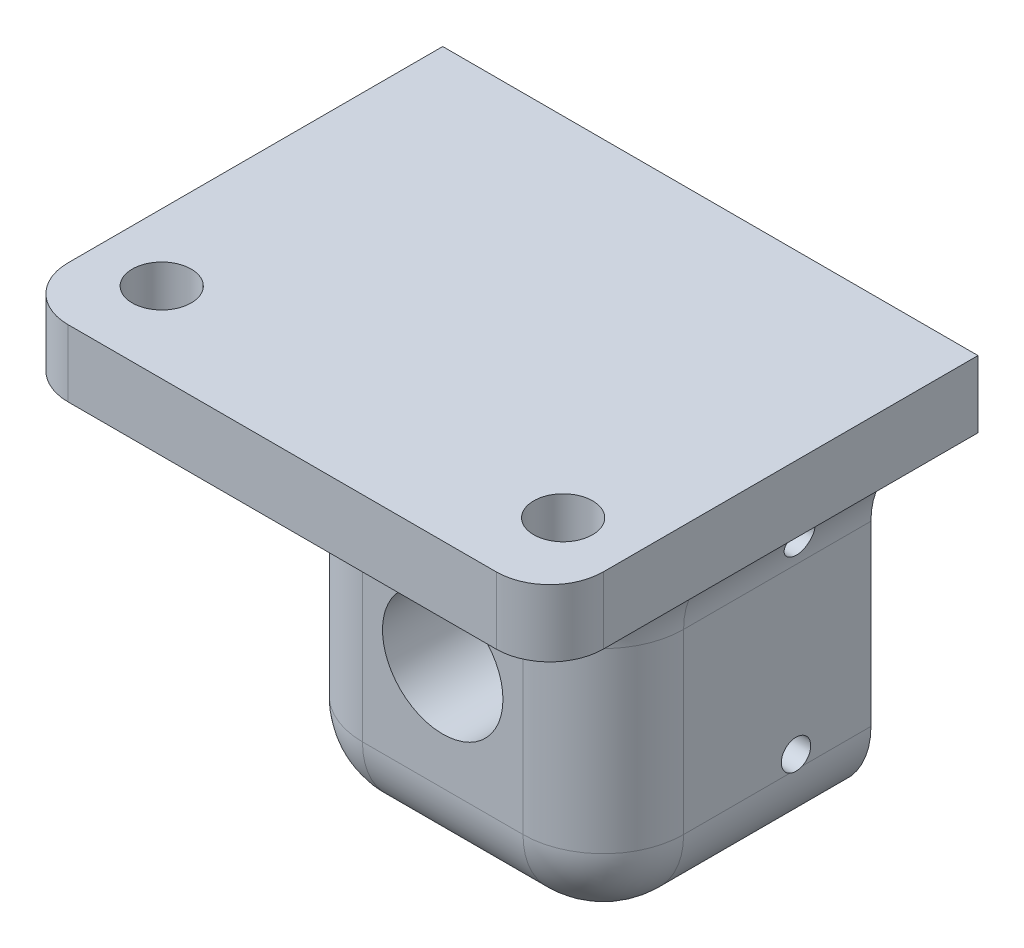
SolidWorks part; units mm, degrees
ref_plane "Plan de face" through (0, 0, 0) normal (0, 0, 1) x (1, 0, 0)
ref_plane "Plan de dessus" through (0, 0, 0) normal (0, 1, 0) x (1, 0, 0)
ref_plane "Plan de droite" through (0, 0, 0) normal (1, 0, 0) x (0, 0, -1)
sketch "Esquisse1" plane through (0, 0, 0) normal (0, 0, 1) x (1, 0, 0)
  line L1 (-20, 17) -> (20, 17)
  line L2 (-20, 17) -> (-20, -17)
  line L3 (-20, -17) -> (20, -17)
  line L4 (20, 17) -> (20, -17)
  dimension "D1" = 40
  dimension "D2" = 34
  dimension "D3" = 17
  dimension "D4" = 20
extrude "Boss.-Extru.1" add sketch "Esquisse1" along normal blind 20
sketch "Esquisse2" plane through (0, 0, 20) normal (0, 0, 1) x (1, 0, 0)
  line L1 (20, 17) -> (-20, 17)
  line L2 (20, 17) -> (20, 12)
  line L3 (20, 12) -> (-20, 12)
  line L4 (-20, 17) -> (-20, 12)
  line L5 (-20, 17) -> (-20, -17) construction
  dimension "D1" = 5
extrude "Boss.-Extru.3" add sketch "Esquisse2" along normal blind 20
sketch "Esquisse4" plane through (0, 0, 20) normal (0, 0, 1) x (1, 0, 0)
  line L0 (20, -17) -> (20, 12) construction
  line L1 (-20, -17) -> (20, -17) construction
  circle A0 centre (0, -3) radius 4.5
  dimension "D1" = 9
  dimension "D2" = 20
  dimension "D3" = 14
extrude "Enlèv. mat.-Extru.1" cut sketch "Esquisse4" against normal through all
sketch "Esquisse5" plane through (0, 0, 0) normal (0, 0, -1) x (-1, 0, 0)
  circle A0 centre (0, -3) radius 8.1
  dimension "D1" = 16.2
extrude "Enlèv. mat.-Extru.2" cut sketch "Esquisse5" against normal blind 12
sketch "Esquisse6" plane through (0, 0, 20) normal (0, 0, 1) x (1, 0, 0)
  line L0 (-20, 12) -> (-12, 5)
  line L1 (-12, 5) -> (-12, -17)
  line L2 (-20, -17) -> (20, -17) construction
  line L3 (-12, -17) -> (-20, -17)
  line L4 (-20, -17) -> (-20, 12)
  line L5 (20, 12) -> (12, 5)
  line L6 (12, 5) -> (12, -17)
  line L7 (12, -17) -> (20, -17)
  line L8 (20, -17) -> (20, 12)
  dimension "D1" = 8
  dimension "D2" = 8
  dimension "D3" = 22
  dimension "D4" = 22
extrude "Enlèv. mat.-Extru.3" cut sketch "Esquisse6" against normal through all
fillet "Congé3" radius 6 2 edges at (12, -17, 10) (-12, -17, 10)
fillet "Congé4" radius 6 2 edges at (12, 5, 10) (-12, 5, 10)
sketch "Esquisse7" plane through (-12, 0, 0) normal (-1, 0, 0) x (0, 0, 1)
  line L1 (12, 5.1) -> (12, -11.1) construction
  line L3 (20, -17) -> (0, -17) construction
  circle A0 centre (5.6, 4) radius 1.1
  circle A1 centre (5.6, -10) radius 1.1
  dimension "D1" = 2.2
  dimension "D2" = 2.2
  dimension "D3" = 14
  dimension "D4" = 6.4
  dimension "D5" = 7
extrude "Enlèv. mat.-Extru.4" cut sketch "Esquisse7" against normal through all and the other way through all
fillet "Congé5" radius 6 9 edges at (-12.5362, 4.7567, 20) (-12, -4.3613, 20) (-10.2426, -15.2426, 20) (0, -17, 20) (10.2426, -15.2426, 20) (12, -4.3613, 20) (12.5362, 4.7567, 20)
sketch "Esquisse8" plane through (0, 12, 0) normal (0, -1, 0) x (1, 0, 0)
  line L0 (-20, 40) -> (20, 40) construction
  line L1 (-20, 40) -> (-20, 14) construction
  circle A0 centre (-15, 26) radius 2.2
  circle A1 centre (15, 26) radius 2.2
  dimension "D2" = 4.4
  dimension "D3" = 4.4
  dimension "D1" = 30
  dimension "D4" = 14
  dimension "D5" = 5
  dimension "D6" = 14
extrude "Enlèv. mat.-Extru.5" cut sketch "Esquisse8" against normal through all
sketch "Esquisse10" plane through (0, 0, 12) normal (0, 0, -1) x (-1, 0, 0)
  circle A0 centre (0, -3) radius 4.5
extrude "Boss.-Extru.4" add sketch "Esquisse10" against normal blind 1
sketch "Esquisse11" plane through (0, 12, 0) normal (0, -1, 0) x (1, 0, 0)
  line L0 (20, 40) -> (20, 14) construction
  line L1 (-20, 40) -> (20, 40)
  line L2 (-20, 40) -> (-20, 32)
  line L3 (-20, 32) -> (20, 32)
  line L4 (20, 40) -> (20, 32)
  dimension "D1" = 8
extrude "Enlèv. mat.-Extru.6" cut sketch "Esquisse11" against normal through all
fillet "Congé6" radius 4 2 edges at (-20, 14.5, 32) (20, 14.5, 32)
